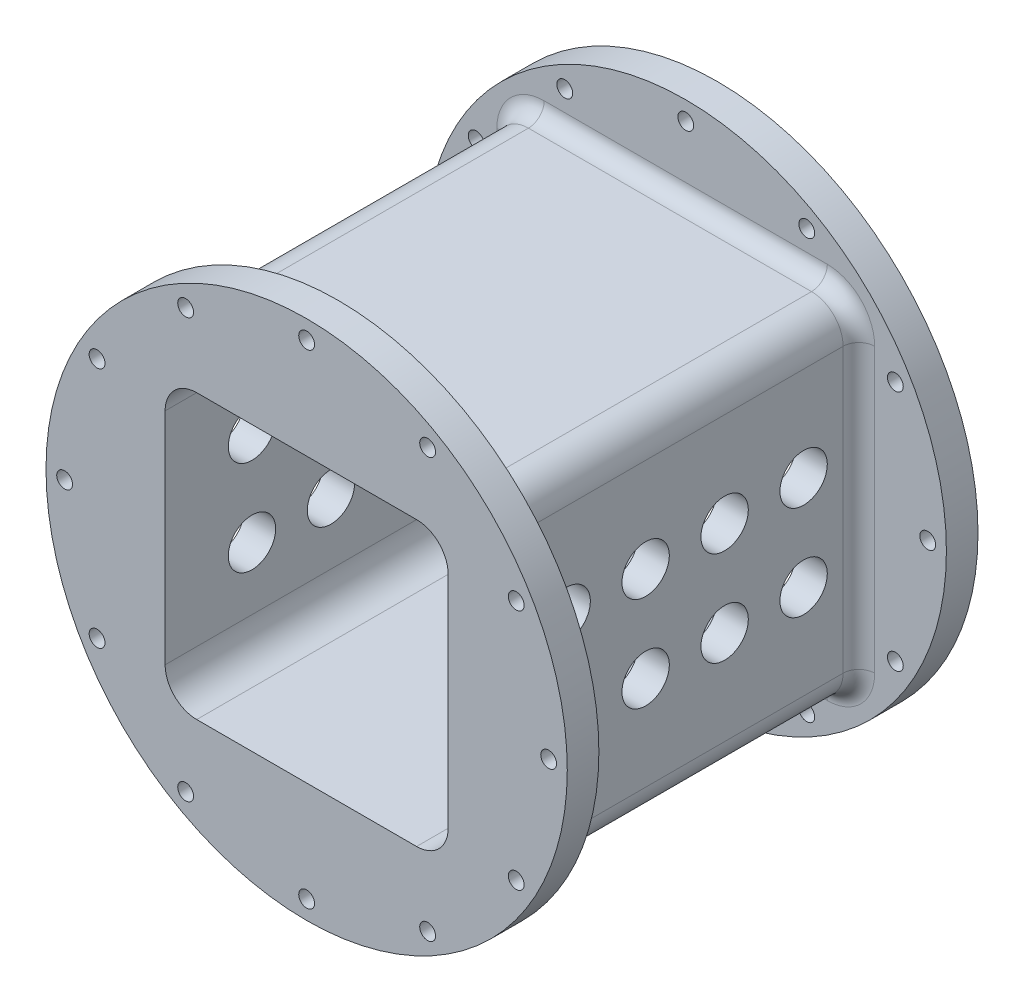
SolidWorks part; units mm, degrees
ref_plane "Front Plane" through (0, 0, 0) normal (0, 0, 1) x (1, 0, 0)
ref_plane "Top Plane" through (0, 0, 0) normal (0, 1, 0) x (1, 0, 0)
ref_plane "Right Plane" through (0, 0, 0) normal (1, 0, 0) x (0, 0, -1)
sketch "Sketch2" plane through (0, 0, 0) normal (0, 0, 1) x (1, 0, 0)
  line L1 (-69.597, -69.597) -> (69.597, -69.597)
  line L2 (-69.597, -69.597) -> (-69.597, 69.597)
  line L3 (-69.597, 69.597) -> (69.597, 69.597)
  line L5 (69.597, 69.597) -> (69.597, -69.597)
  line L6 (-69.597, 69.597) -> (69.597, -69.597) construction
  line L10 (69.597, 69.597) -> (-69.597, -69.597) construction
  line L11 (56.897, 56.897) -> (56.897, -56.897)
  line L12 (-56.897, -56.897) -> (56.897, -56.897)
  line L13 (-56.897, -56.897) -> (-56.897, 56.897)
  line L14 (-56.897, 56.897) -> (56.897, 56.897)
  circle A0 centre (0, 0) radius 104.775 construction
  circle A1 centre (0, 0) radius 98.425 construction
  point P0 (0, 0)
  point P3 (0, 0)
  point P8 (0, 0)
  point P10 (-69.5954, 69.5986)
  dimension "D1" = 209.55
  dimension "D2" = 6.35
  dimension "D3" = 12.7
extrude "Boss-Extrude1" add sketch "Sketch2" along normal mid plane 152.4 contours L3 L5 L1 L2
sketch "Sketch3" plane through (0, 0, 76.2) normal (0, 0, 1) x (1, 0, 0)
  circle A0 centre (0, 0) radius 104.775
  dimension "D1" = 209.55
extrude "Boss-Extrude2" add sketch "Sketch3" along normal mid plane 12.7
sketch "Sketch4" plane through (0, 0, -76.2) normal (0, 0, -1) x (-1, 0, 0)
  circle A0 centre (0, 0) radius 104.775 construction
  circle A1 centre (0, 0) radius 104.775
extrude "Boss-Extrude3" add sketch "Sketch4" along normal mid plane 12.7
extrude "Cut-Extrude1" cut sketch "Sketch2<3>" against normal through all both and the other way through all contours L14 L11 L12 L13
sketch "Sketch2<3>" plane through (0, 0, 0) normal (0, 0, 1) x (1, 0, 0) same geometry as "Sketch2"
fillet "Fillet1" radius 12.7 8 edges at (69.597, -69.597, 0) (-69.597, -69.597, 0) (-56.897, -56.897, 0) (56.897, -56.897, 0) (56.897, 56.897, 0) (-56.897, 56.897, 0) (69.597, 69.597, 0) (-69.597, 69.597, 0)
sketch "Sketch6" plane through (0, 0, 82.55) normal (0, 0, 1) x (1, 0, 0)
  line L0 (0, 0) -> (0, 104.775) construction
  line L1 (0, 104.775) -> (0, 0) construction
  line L2 (0, 0) -> (48.641, 84.2487) construction
  circle A0 centre (0, 0) radius 104.775 construction
  circle A1 centre (48.641, 84.2487) radius 3.1826
  circle A2 centre (0, 0) radius 97.282 construction
  dimension "D2" = 6.3652
  dimension "D1" = 30
  dimension "D3" = 97.282
extrude "Cut-Extrude2" cut sketch "Sketch6" against normal through all both
pattern_circular "CirPattern1" count 12 over 360 about axis through (0, 0, 82.55) along (0, 0, -1) of "Cut-Extrude2"
sketch "Sketch8" plane through (-69.597, 0, 0) normal (-1, 0, 0) x (0, 0, 1)
  line L0 (0, 0) -> (145.5831, 0) construction
  line L1 (145.5831, 0) -> (0, 0) construction
  line L2 (0, -19.05) -> (0, 19.05) construction
  line L3 (-47.625, 19.05) -> (-15.875, 19.05) construction
  line L4 (-15.875, 19.05) -> (15.875, 19.05) construction
  line L5 (15.875, 19.05) -> (47.625, 19.05) construction
  line L6 (15.875, -19.05) -> (47.625, -19.05) construction
  line L7 (-15.875, -19.05) -> (15.875, -19.05) construction
  line L8 (-47.625, -19.05) -> (-15.875, -19.05) construction
  circle A0 centre (-47.625, 19.05) radius 9.525
  circle A1 centre (47.625, 19.05) radius 9.525
  circle A2 centre (-15.875, 19.05) radius 9.525
  circle A3 centre (15.875, 19.05) radius 9.525
  circle A4 centre (15.875, -19.05) radius 9.525
  circle A5 centre (-15.875, -19.05) radius 9.525
  circle A6 centre (47.625, -19.05) radius 9.525
  circle A7 centre (-47.625, -19.05) radius 9.525
  point P9 (0, 19.05)
  point P13 (0, 0)
  point P14 (0, 19.05)
  point P15 (51.2295, 19.8059)
  point P25 (0, -19.05)
  point P26 (145.5831, 0)
  dimension "D1" = 19.05
  dimension "D2" = 31.75
  dimension "D3" = 19.05
extrude "Cut-Extrude3" cut sketch "Sketch8" against normal through all
fillet "Fillet2" radius 6.35 16 edges at (65.8772, 65.8772, -69.85) (69.597, 0, -69.85) (65.8772, -65.8772, -69.85) (0, -69.597, -69.85) (-65.8772, -65.8772, -69.85) (-69.597, 0, -69.85) (-65.8772, 65.8772, -69.85) (-65.8772, 65.8772, 69.85) (-69.597, 0, 69.85) (-65.8772, -65.8772, 69.85) (0, -69.597, 69.85) (65.8772, -65.8772, 69.85) (69.597, 0, 69.85) (65.8772, 65.8772, 69.85) (0, 69.597, -69.85) (0, 69.597, 69.85)
equation "\"n\"= 12"
equation "\"D1@Sketch6\"=360 / \"n\""
equation "\"D1@CirPattern1\"=\"n\""
